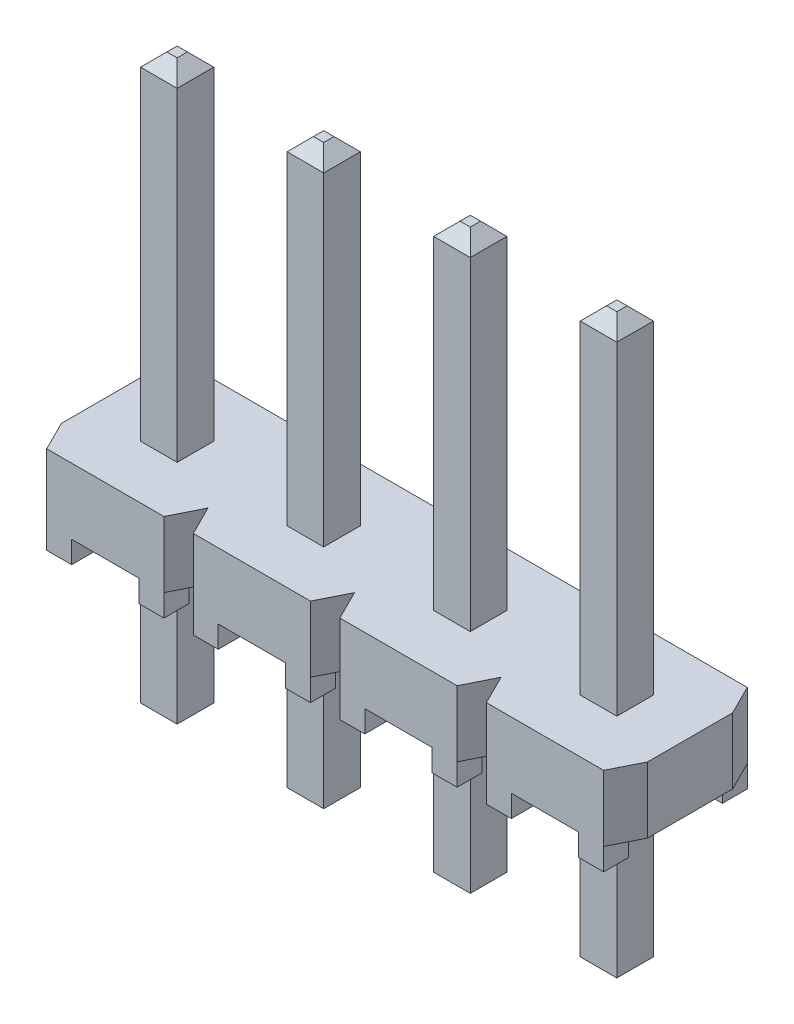
SolidWorks part; units mm, degrees
ref_plane "Front" through (0, 0, 0) normal (0, 0, 1) x (1, 0, 0)
ref_plane "Top" through (0, 0, 0) normal (0, 1, 0) x (1, 0, 0)
ref_plane "Side" through (0, 0, 0) normal (1, 0, 0) x (0, 0, -1)
sketch "Sketch1" plane through (0, 0, 0) normal (0, 1, 0) x (1, 0, 0)
  line L0 (5.08, -1.2446) -> (-5.08, 1.2446) construction
  line L1 (-5.08, 1.2446) -> (5.08, 1.2446)
  line L2 (-5.08, 1.2446) -> (-5.08, -1.2446)
  line L3 (-5.08, -1.2446) -> (5.08, -1.2446)
  line L4 (5.08, 1.2446) -> (5.08, -1.2446)
  dimension "D1" = 10.16
  dimension "D2" = 2.4892
extrude "Base-Extrude" add sketch "Sketch1" along normal mid plane 1.143
sketch "Sketch3" plane through (0, 0.5715, 0) normal (0, 1, 0) x (-1, 0, 0)
  line L0 (7.5339, 0) -> (10.4044, 0) construction
  line L1 (2.286, 1.2446) -> (2.794, 1.2446)
  line L2 (2.286, -1.2446) -> (2.794, -1.2446)
  line L3 (2.794, 1.2446) -> (2.54, 0.7366)
  line L4 (2.794, -1.2446) -> (2.54, -0.7366)
  line L5 (2.54, 0.7366) -> (2.286, 1.2446)
  line L6 (2.54, -0.7366) -> (2.286, -1.2446)
  line L7 (2.54, 1.2446) -> (2.54, 0.7366) construction
  line L8 (2.54, -1.2446) -> (2.54, -0.7366) construction
  line L9 (5.08, 1.2446) -> (-5.08, 1.2446) construction
  line L11 (3.81, -1.4521) -> (3.81, 2.3817) construction
  line L12 (5.08, -0.7366) -> (5.334, -1.2446)
  line L13 (5.08, 0.7366) -> (5.334, 1.2446)
  line L14 (4.826, -1.2446) -> (5.08, -0.7366)
  line L15 (4.826, 1.2446) -> (5.08, 0.7366)
  line L16 (5.334, -1.2446) -> (4.826, -1.2446)
  line L17 (5.334, 1.2446) -> (4.826, 1.2446)
  line L18 (5.08, -1.2446) -> (5.08, 1.2446) construction
  dimension "D1" = 0.508
  dimension "D2" = 0.508
  dimension "D3" = 1.27
  dimension "D4" = 1.27
extrude "Snap Grooves" cut sketch "Sketch3" against normal through all
sketch "Sketch4" plane through (0, -0.5715, 0) normal (0, -1, 0) x (1, 0, 0)
  line L0 (-3.81, 1.3819) -> (-3.81, -1.499) construction
  line L1 (-4.826, 1.2446) -> (-2.794, 1.2446) construction
  line L2 (-4.826, 1.2446) -> (-4.3942, 1.2446)
  line L3 (-4.826, 1.2446) -> (-4.826, 0.8128)
  line L4 (-4.826, 0.8128) -> (-4.3942, 0.8128)
  line L5 (-4.3942, 1.2446) -> (-4.3942, 0.8128)
  line L6 (-3.2258, 1.2446) -> (-3.2258, 0.8128)
  line L7 (-2.794, 0.8128) -> (-3.2258, 0.8128)
  line L8 (-2.794, 1.2446) -> (-2.794, 0.8128)
  line L9 (-2.794, 1.2446) -> (-3.2258, 1.2446)
  line L11 (-5.08, -0.7366) -> (-5.08, 0.7366) construction
  line L12 (-9.3213, 0) -> (-10.8923, 0) construction
  line L14 (-2.794, -1.2446) -> (-3.2258, -1.2446)
  line L15 (-2.794, -1.2446) -> (-2.794, -0.8128)
  line L16 (-2.794, -0.8128) -> (-3.2258, -0.8128)
  line L17 (-3.2258, -1.2446) -> (-3.2258, -0.8128)
  line L18 (-4.3942, -1.2446) -> (-4.3942, -0.8128)
  line L19 (-4.826, -0.8128) -> (-4.3942, -0.8128)
  line L20 (-4.826, -1.2446) -> (-4.826, -0.8128)
  line L21 (-4.826, -1.2446) -> (-4.3942, -1.2446)
  dimension "D1" = 0.4318
  dimension "D2" = 0.4318
  dimension "D3" = 1.27
extrude "Standoffs" add sketch "Sketch4" along normal blind 0.381
pattern_linear "Position Pattern" count 4 spacing 2.54 along (1, 0, 0) of "Snap Grooves", "Standoffs"
ref_plane "Position 1 Plane" through (-3.81, 0, 0) normal (-1, 0, 0) x (0, 0, 1)
sketch "Sketch5" plane through (-3.81, 0, 0) normal (-1, 0, 0) x (0, 0, 1)
  line L0 (0, 6.4135) -> (0, -3.5865) construction
  line L1 (-0.3175, 6.4135) -> (0.3175, 6.4135)
  line L2 (-0.3175, 6.4135) -> (-0.3175, -3.5865)
  line L3 (-0.3175, -3.5865) -> (0.3175, -3.5865)
  line L4 (0.3175, 6.4135) -> (0.3175, -3.5865)
  line L5 (1.2446, -0.5715) -> (1.2446, 0.5715) construction
  line L6 (-0.7366, 0.5715) -> (0.7366, 0.5715) construction
  dimension "D1" = 1.2446
  dimension "D2" = 0.635
  dimension "D3" = 5.842
  dimension "D4" = 10
extrude "Terminal -TH" add sketch "Sketch5" along normal mid plane 0.635
chamfer "T1 Tip1" distance 0.2286 angle 45 8 edges at (-3.4925, 6.4135, 0) (-3.81, 6.4135, -0.3175) (-4.1275, 6.4135, 0) (-3.81, 6.4135, 0.3175) (-3.81, -3.5865, -0.3175) (-4.1275, -3.5865, 0) (-3.81, -3.5865, 0.3175) (-3.4925, -3.5865, 0)
pattern_linear "Terminal Pattern" count 1 spacing 2.54 along (0, 0, -1) count 4 spacing 2.54 along (1, 0, 0) of "Terminal -TH", "T1 Tip1"
ref_plane "Initial -S Polarize Plane" through (6.35, 0, 0) normal (1, 0, 0) x (0, 0, -1)
ref_plane "-S Polarize Plane" through (3.81, 0, 0) normal (1, 0, 0) x (0, 0, -1)
ref_plane "Initial -D Polarize Plane" through (-6.35, 0, 0) normal (-1, 0, 0) x (0, 0, 1)
ref_plane "-D Polarize Plane" through (-5.08, 0, 0) normal (-1, 0, 0) x (0, 0, 1)
